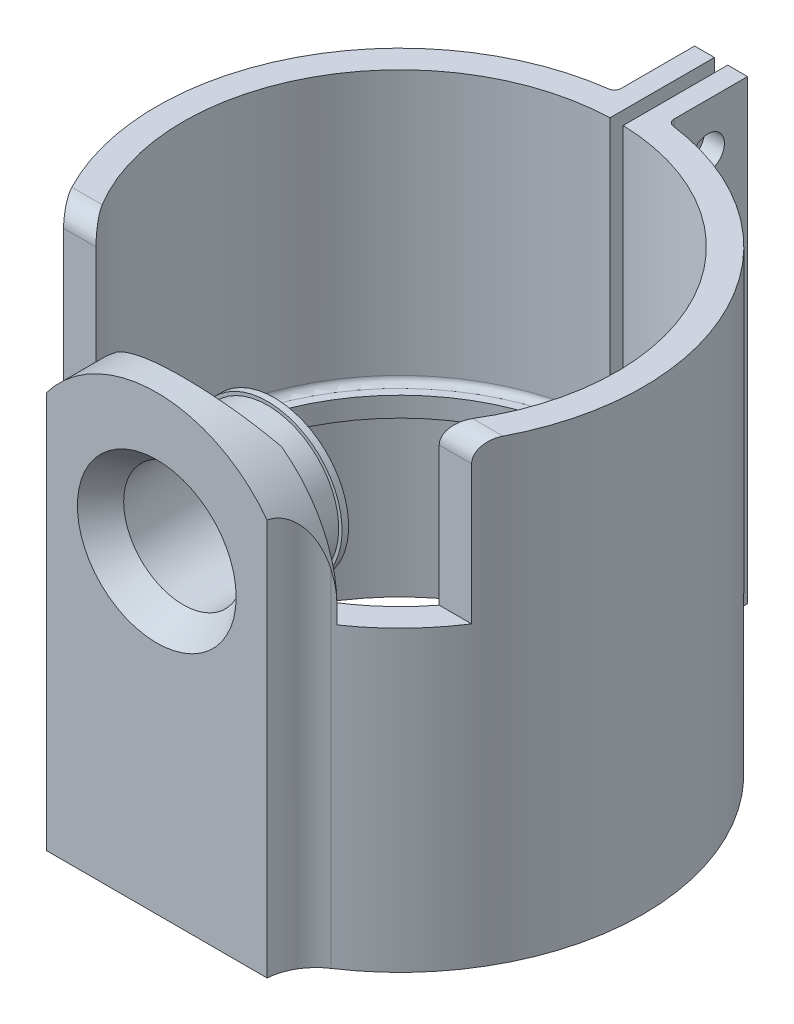
SolidWorks part; units mm, degrees
ref_plane "Спереди" through (0, 0, 0) normal (0, 0, 1) x (1, 0, 0)
ref_plane "Сверху" through (0, 0, 0) normal (0, 1, 0) x (1, 0, 0)
ref_plane "Справа" through (0, 0, 0) normal (1, 0, 0) x (0, 0, -1)
sketch "Эскиз1" plane through (0, 0, 0) normal (0, 1, 0) x (1, 0, 0)
  line L0 (0, 0) -> (0, -43.0119) construction
  line L2 (-16.6733, -36.75) -> (16.6733, -36.75)
  line L3 (-16.6733, -36.75) -> (-16.6733, -32.75)
  line L5 (16.6733, -36.75) -> (16.6733, -32.75)
  arc A0 (-16.6733, -32.75) -> (16.6733, -32.75) centre (0, 0) cw
  circle A1 centre (0, 0) radius 32.75
  dimension "D1" = 65.5
  dimension "D2" = 36.75
  dimension "D3" = 4
extrude "main" add sketch "Эскиз1" along normal blind 44 and the other way blind 25
sketch "Эскиз2" plane through (0, 0, 0) normal (0, 0, 1) x (1, 0, 0)
  circle A0 centre (0, 22.5) radius 11
  dimension "D1" = 22
  dimension "D2" = 22.5
extrude "hole" cut sketch "Эскиз2" along normal through all
sketch "Эскиз3" plane through (0, 0, 0) normal (0, 1, 0) x (1, 0, 0)
  circle A0 centre (0, 0) radius 32.75
  circle A1 centre (0, 0) radius 30.5
  circle A3 centre (0, 0) radius 32.75 construction
  dimension "D1" = 61
extrude "stop" add sketch "Эскиз3" along normal blind 3
sketch "Эскиз4" plane through (0, 0, 0) normal (0, 1, 0) x (1, 0, 0)
  line L0 (4, 36.5317) -> (0, 0) construction
  line L1 (0, 0) -> (-4, 36.5317) construction
  line L2 (0, 0) -> (0, 39.0687) construction
  line L3 (-4, 36.5317) -> (-4, 48.5317)
  line L4 (-4, 48.5317) -> (4, 48.5317)
  line L5 (4, 48.5317) -> (4, 36.5317)
  arc A0 (-4, 36.5317) -> (4, 36.5317) centre (0, 0) cw
  arc A1 (16.6733, -32.75) -> (-16.6733, -32.75) centre (0, 0) ccw construction
  dimension "D1" = 4
  dimension "D2" = 4
  dimension "D3" = 12
extrude "lock" add sketch "Эскиз4" against normal up to surface (25 mm away) and the other way up to surface (44 mm away) up to face at (0, -25, 32.75) other way up to face at (0, 44, 17.375)
sketch "Эскиз5" plane through (0, 0, 0) normal (0, 1, 0) x (1, 0, 0)
  line L0 (4, 48.5317) -> (-4, 48.5317) construction
  line L1 (-1, 0) -> (1, 0)
  line L2 (-1, 0) -> (-1, 48.5317)
  line L3 (-1, 48.5317) -> (1, 48.5317)
  line L4 (1, 0) -> (1, 48.5317)
  dimension "D1" = 1
extrude "slot" cut sketch "Эскиз5" against normal through all and the other way through all
sketch "Эскиз6" plane through (4, 0, 0) normal (1, 0, 0) x (0, 0, -1)
  line L0 (42.5317, 7.5457) -> (42.5317, -34.4595) construction
  line L1 (48.5317, -25) -> (36.5317, -25) construction
  line L3 (36.5317, 44) -> (48.5317, 44) construction
  circle A0 centre (42.5317, 37) radius 2.5
  circle A1 centre (42.5317, -18) radius 2.5
  point P4 (42.5317, -25)
  dimension "D1" = 7
  dimension "D2" = 5
  dimension "D3" = 7
extrude "small holes" cut sketch "Эскиз6" against normal through all
ref_plane "Плоскость1" through (0, 0, 20) normal (0, 0, 1) x (1, 0, 0)
sketch "Эскиз10" plane through (0, 0, 0) normal (1, 0, 0) x (0, 0, -1)
  line L0 (-20, 40.425) -> (-20, -40.425) construction
  line L1 (-20, 20.0487) -> (-30.3, 20.0487)
  line L2 (-20, 20.0487) -> (-20, 60)
  line L3 (-20, 60) -> (-30.3, 60)
  line L4 (-30.3, 20.0487) -> (-30.3, 60)
  dimension "D1" = 10.3
extrude "key slot" cut sketch "Эскиз10" against normal through all and the other way through all
sketch "Эскиз9" plane through (0, 0, 20) normal (0, 0, 1) x (1, 0, 0)
  circle A0 centre (0, 22.5) radius 9
  circle A1 centre (0, 22.5) radius 11
  dimension "D2" = 18
  dimension "D3" = 22
  dimension "D1" = 22.5
extrude "tube" add sketch "Эскиз9" along normal up to surface (16.75 mm away) up to face at (0, 9.5, 36.75)
sketch "Эскиз11" plane through (0, 0, 20) normal (0, 0, -1) x (-1, 0, 0)
  circle A0 centre (0, 22.5) radius 13
  circle A2 centre (0, 22.5) radius 10.75
  circle A3 centre (0, 22.5) radius 9 construction
  dimension "D1" = 21.5
  dimension "D2" = 26
extrude "tube slot" cut sketch "Эскиз11" against normal up to surface (10.3 mm away) up to face at (-16.6123, 32.0244, 30.3)
chamfer "Фаска1" distance 3 distance2 4 1 edges at (9, 22.5, 36.75) first distance on face at (0, 9.5, 36.75)
sketch "Эскиз12" plane through (0, 0, 20) normal (0, 0, -1) x (-1, 0, 0)
  circle A0 centre (0, 22.5) radius 11.25
  circle A1 centre (0, 22.5) radius 9
  circle A2 centre (0, 22.5) radius 9 construction
  dimension "D1" = 22.5
extrude "tube stop" add sketch "Эскиз12" along normal blind 1
sketch "Эскиз14" plane through (0, 0, 20) normal (0, 0, 1) x (1, 0, 0)
  line L2 (-20.796, 22.5) -> (-20.796, 44)
  line L3 (-20.796, 44) -> (20.796, 44)
  line L4 (20.796, 44) -> (20.796, 22.5)
  arc A0 (-20.796, 22.5) -> (20.796, 22.5) centre (0, 22.5) cw
  circle A2 centre (0, 22.5) radius 11 construction
extrude "tube external" cut sketch "Эскиз14" along normal through all
fillet "Скругление3" radius 8 2 edges at (-16.6733, 4.9643, 32.75) (16.6733, 4.9643, 32.75)
fillet "Скругление5" radius 1 1 edges at (0, 3, 32.75)
fillet "Скругление6" radius 1 2 edges at (4, 9.5, -36.5317) (-4, 9.5, -36.5317)
fillet "Скругление7" radius 3 2 edges at (28.3825, 44, 20) (-28.3825, 44, 20)
